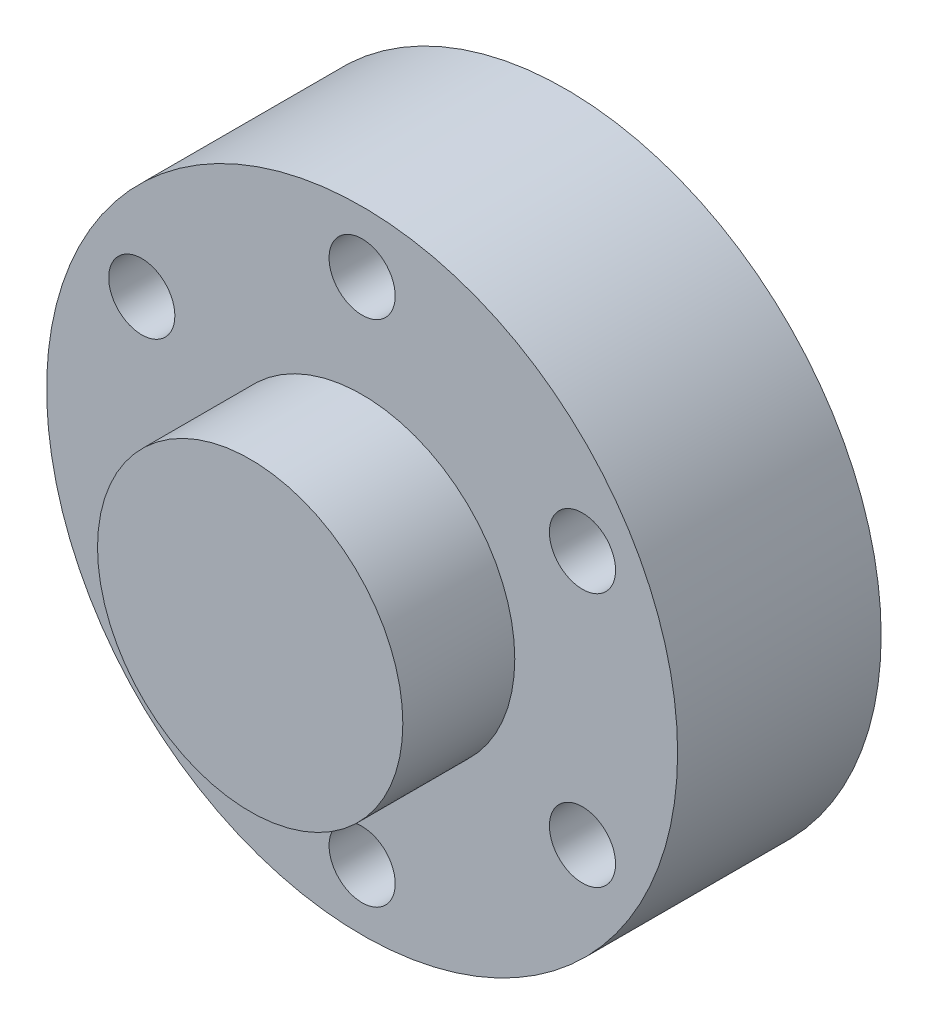
SolidWorks part; units mm, degrees
ref_plane "Front Plane" through (0, 0, 0) normal (0, 0, 1) x (1, 0, 0)
ref_plane "Top Plane" through (0, 0, 0) normal (0, 1, 0) x (1, 0, 0)
ref_plane "Right Plane" through (0, 0, 0) normal (1, 0, 0) x (0, 0, -1)
sketch "Sketch2" plane through (0, 0, 0) normal (0, 0, 1) x (1, 0, 0)
  line L0 (0, 20.3178) -> (0, -21.083) construction
  circle A0 centre (0, 0) radius 9.5
  circle A1 centre (0, 0) radius 12.5 construction
  circle A3 centre (0, 0) radius 15.5
  circle A4 centre (0, 12.5) radius 1.625
  circle A5 centre (10.8253, 6.25) radius 1.625
  circle A6 centre (10.8253, -6.25) radius 1.625
  circle A7 centre (0, -12.5) radius 1.625
  circle A8 centre (-10.8253, -6.25) radius 1.625
  circle A9 centre (-10.8253, 6.25) radius 1.625
  point P21 (1.7321, -1)
  point P22 (0, 0)
  dimension "D1" = 19
  dimension "D2" = 6
  dimension "D3" = 25
  dimension "D4" = 31
  dimension "D5" = 3.25
extrude "Boss-Extrude1" add sketch "Sketch2" along normal blind 10 contours A3 A9 A8 A7 A6 A5 A4 A0 | A0 region at (0, 0, 0) region at (-15.0616, 0, 0)
sketch "Sketch3" plane through (0, 0, 10) normal (0, 0, 1) x (1, 0, 0)
  circle A0 centre (0, 0) radius 7.5
  dimension "D1" = 15
extrude "Boss-Extrude2" add sketch "Sketch3" along normal blind 5.5
sketch "Sketch6" plane through (0, 0, 0) normal (0, 0, -1) x (-1, 0, 0)
  circle A0 centre (0, 0) radius 7.5
  dimension "D1" = 15
extrude "Boss-Extrude4" add sketch "Sketch6" along normal blind 5.5 contours A0
sketch "Sketch7" plane through (0, 0, -5.5) normal (0, 0, -1) x (-1, 0, 0)
  circle A0 centre (0, 0) radius 2
  dimension "D1" = 4
extrude "Boss-Extrude5" add sketch "Sketch7" along normal blind 1
fillet "Fillet2" radius 0.05 1 edges at (-2, 0, -6.5)
sketch "Sketch9" plane through (0, 0, -6.5) normal (0, 0, -1) x (-1, 0, 0)
  line L1 (-1.2247, 1.25) -> (1.2247, 1.25)
  arc A0 (-1.2247, 1.25) -> (1.2247, 1.25) centre (0, 0) ccw
  circle A1 centre (0, -0.25) radius 1.5 construction
  dimension "D1" = 3.5
  dimension "D2" = 3
extrude "Cut-Extrude1" cut sketch "Sketch9" against normal blind 11
